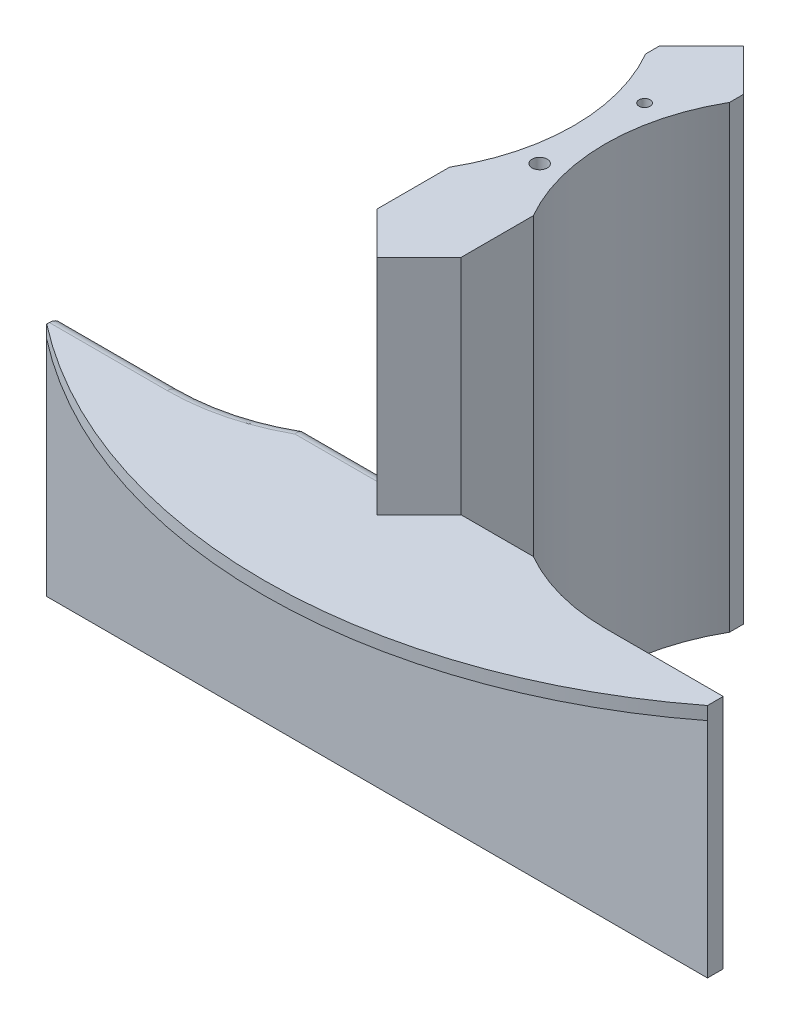
SolidWorks part; units mm, degrees
ref_plane "Front Plane" through (0, 0, 0) normal (0, 0, 1) x (1, 0, 0)
ref_plane "Top Plane" through (0, 0, 0) normal (0, 1, 0) x (1, 0, 0)
ref_plane "Right Plane" through (0, 0, 0) normal (1, 0, 0) x (0, 0, -1)
sketch "Sketch1" plane through (0, 0, 0) normal (0, 1, 0) x (1, 0, 0)
  line L0 (23.7595, 41.275) -> (41.275, 41.275) construction
  line L1 (-41.275, -41.275) -> (-23.7595, -41.275) construction
  line L2 (-41.275, -41.275) -> (-41.275, -23.7595) construction
  line L3 (-41.275, 41.275) -> (-23.7595, 41.275) construction
  line L4 (41.275, -41.275) -> (41.275, -23.7595) construction
  line L5 (-41.275, -41.275) -> (41.275, 41.275) construction
  line L6 (-41.275, 41.275) -> (41.275, -41.275) construction
  line L7 (41.275, 23.7595) -> (41.275, 41.275) construction
  line L8 (-41.275, 23.7595) -> (-41.275, 41.275) construction
  line L9 (23.7595, -41.275) -> (41.275, -41.275) construction
  line L10 (24.7569, 45.085) -> (45.085, 45.085) construction
  line L11 (45.085, 24.7569) -> (45.085, 45.085) construction
  line L12 (45.085, -45.085) -> (45.085, -24.7569) construction
  line L13 (24.7569, -45.085) -> (45.085, -45.085) construction
  line L14 (-45.085, -45.085) -> (-24.7569, -45.085) construction
  line L15 (-45.085, -45.085) -> (-45.085, -24.7569) construction
  line L16 (-45.085, 24.7569) -> (-45.085, 45.085) construction
  line L17 (-45.085, 45.085) -> (-24.7569, 45.085) construction
  line L19 (-51.435, -51.435) -> (51.435, -51.435) construction
  line L20 (-51.435, -51.435) -> (-51.435, 51.435) construction
  line L21 (-51.435, 51.435) -> (51.435, 51.435) construction
  line L22 (51.435, -51.435) -> (51.435, 51.435) construction
  line L23 (-51.435, -51.435) -> (51.435, 51.435) construction
  line L24 (-51.435, 51.435) -> (51.435, -51.435) construction
  arc A1 (-41.275, 23.7595) -> (-41.275, -23.7595) centre (0, 0) ccw construction
  arc A2 (23.7595, 41.275) -> (-23.7595, 41.275) centre (0, 0) ccw construction
  arc A3 (-23.7595, -41.275) -> (23.7595, -41.275) centre (0, 0) ccw construction
  arc A4 (41.275, -23.7595) -> (41.275, 23.7595) centre (0, 0) ccw construction
  arc A5 (45.085, -24.7569) -> (45.085, 24.7569) centre (0, 0) ccw construction
  arc A6 (-24.7569, -45.085) -> (24.7569, -45.085) centre (0, 0) ccw construction
  arc A7 (-45.085, 24.7569) -> (-45.085, -24.7569) centre (0, 0) ccw construction
  arc A8 (24.7569, 45.085) -> (-24.7569, 45.085) centre (0, 0) ccw construction
  point P0 (0, 0)
  dimension "D1" = 82.55
  dimension "D2" = 82.55
  dimension "D3" = 95.25
  dimension "D4" = 3.81
sketch "Sketch2" plane through (0, 0, 0) normal (0, 0, 1) x (1, 0, 0)
  line L0 (0, 48) -> (0, 0) construction
  line L1 (0, 0) -> (0, -9.15) construction
  line L2 (0, 48) -> (0, 101.975) construction
  dimension "Cage height" = 48
  dimension "Plate height" = 53.975
  dimension "D1" = 57.15
  dimension "D2" = 9.15
sketch "Sketch13" plane through (0, 0, 0) normal (0, 1, 0) x (1, 0, 0)
  line L0 (-51.435, -51.435) -> (51.435, -51.435) construction
  line L1 (-41.275, -41.275) -> (-23.7595, -41.275) construction
  line L2 (-41.275, -41.275) -> (-41.275, -23.7595) construction
  line L4 (-51.435, -51.435) -> (0, -51.435)
  line L5 (-41.275, -41.275) -> (-23.7595, -41.275)
  line L6 (-41.275, -41.275) -> (-41.275, -23.7595)
  line L9 (0, -47.625) -> (0, -51.435)
  line L10 (-51.435, 51.435) -> (51.435, -51.435) construction
  line L11 (-41.275, 23.7595) -> (-41.275, 41.275) construction
  line L12 (-51.435, -51.435) -> (-51.435, 51.435) construction
  line L13 (-51.435, 51.435) -> (-41.275, 41.275)
  line L14 (-41.275, 23.7595) -> (-41.275, 41.275)
  line L15 (-51.435, -51.435) -> (-51.435, 51.435)
  arc A0 (-23.7595, -41.275) -> (23.7595, -41.275) centre (0, 0) ccw construction
  arc A2 (-23.7595, -41.275) -> (0, -47.625) centre (0, 0) ccw
  arc A4 (-41.275, 23.7595) -> (-41.275, -23.7595) centre (0, 0) ccw construction
  arc A5 (-41.275, 23.7595) -> (-41.275, -23.7595) centre (0, 0) ccw
extrude "Boss-Extrude2" add sketch "Sketch13" along normal up to vertex (101.975 mm away) and the other way up to vertex (9.15 mm away) up to point (0, 101.975, 0) other way up to point (0, -9.15, 0)
sketch "Sketch15" plane through (0, 101.975, 0) normal (0, 1, 0) x (1, 0, 0)
  line L0 (0, 0) -> (-51.435, -51.435)
  line L1 (-51.435, -51.435) -> (0, -51.435)
  line L2 (0, -51.435) -> (0, 0)
  line L3 (-51.435, -51.435) -> (51.435, -51.435) construction
extrude "Cut-Extrude2" cut sketch "Sketch15" against normal up to vertex (53.975 mm away) up to point (0, 48, 0)
mirror "Mirror1" about plane through (-51.435, 101.975, 51.435) normal (1, 0, 0) of "Boss-Extrude2", "Cut-Extrude2"
sketch "Sketch16" plane through (0, -9.15, 0) normal (0, -1, 0) x (1, 0, 0)
  line L1 (-51.435, -51.435) -> (51.435, -51.435) construction
  circle A5 centre (-51.435, -13.335) radius 1.35
  dimension "D1" = 2.7
  dimension "D2" = 38.1
extrude "Cut-Extrude3" cut sketch "Sketch16" against normal through all
sketch "Sketch17" plane through (0, 101.975, 0) normal (0, 1, 0) x (1, 0, 0)
  line L0 (7.0944, 7.0944) -> (-7.0944, -7.0944)
  line L1 (7.0944, 7.0944) -> (-44.3406, 58.5294)
  line L2 (-7.0944, -7.0944) -> (-51.435, 37.2462)
  line L3 (-44.3406, 58.5294) -> (-51.435, 51.435)
  line L4 (-41.275, -41.275) -> (41.275, 41.275) construction
  line L5 (-61.595, 41.275) -> (-51.435, 51.435) construction
  line L6 (-51.435, -51.435) -> (-51.435, 51.435) construction
  line L7 (-51.435, 7.7321) -> (-51.435, 82.5591) construction
  line L8 (-95.7756, -7.0944) -> (-51.435, 37.2462)
  line L9 (-58.5294, 58.5294) -> (-51.435, 51.435)
  line L10 (-109.9644, 7.0944) -> (-58.5294, 58.5294)
  line L11 (-109.9644, 7.0944) -> (-95.7756, -7.0944)
  dimension "D1" = 20.066
extrude "Cut-Extrude4" cut sketch "Sketch17" against normal through all
sketch "Sketch22" plane through (0, 0, 0) normal (0, 1, 0) x (1, 0, 0)
  line L0 (-51.435, -51.435) -> (-51.435, 51.435) construction
  line L1 (-51.435, 51.435) -> (51.435, 51.435) construction
  circle A0 centre (-51.435, -12.065) radius 1.85
  dimension "D1" = 3.7
  dimension "D2" = 63.5
extrude "Cut-Extrude7" cut sketch "Sketch22" against normal through all both and the other way through all
sketch "Sketch23" plane through (0, 48, 0) normal (0, 1, 0) x (1, 0, 0)
  line L1 (0, -51.435) -> (28.575, -51.435)
  line L2 (0, -51.435) -> (0, -47.625)
  line L3 (0, -47.625) -> (28.575, -47.625)
  line L4 (28.575, -51.435) -> (28.575, -47.625)
  line L6 (-102.87, -51.435) -> (-131.445, -51.435)
  line L7 (-102.87, -51.435) -> (-102.87, -47.625)
  line L8 (-102.87, -47.625) -> (-131.445, -47.625)
  line L9 (-131.445, -51.435) -> (-131.445, -47.625)
  dimension "D1" = 28.575
extrude "Boss-Extrude3" add sketch "Sketch23" against normal up to surface (57.15 mm away) up to face at (-51.435, -9.15, 13.915)
sketch "Sketch24" plane through (0, 48, 0) normal (0, 1, 0) x (1, 0, 0)
  line L0 (28.575, -51.435) -> (-131.445, -51.435)
  arc A0 (-131.445, -51.435) -> (28.575, -51.435) centre (-51.435, 51.435) ccw
extrude "Boss-Extrude4" add sketch "Sketch24" against normal blind 3.175
fillet "Fillet1" radius 3.175 3 edges at (-117.1575, 48, 47.625) (-90.5733, 48, 46.0101) (-70.3527, 48, 41.275)
equation "\"tightTol\"= 0.005in"
equation "\"normTol\"= 0.01in"
equation "\"looseTol\"= 0.02in"
equation "\"Cage height@Sketch2\"=48mm"
equation "\"Plate height@Sketch2\"=1.375+0.75"
equation "\"D1@Sketch17\"=0.75in+2*\"looseTol\""
equation "\"D1@Sketch22\"=3.7mm"
equation "\"D1@Sketch16\"=2.7mm"
